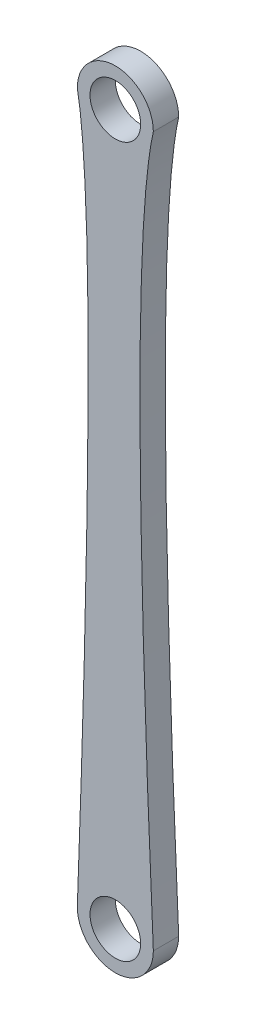
SolidWorks part; units mm, degrees
ref_plane "Front Plane" through (0, 0, 0) normal (0, 0, 1) x (1, 0, 0)
ref_plane "Top Plane" through (0, 0, 0) normal (0, 1, 0) x (1, 0, 0)
ref_plane "Right Plane" through (0, 0, 0) normal (1, 0, 0) x (0, 0, -1)
sketch "Sketch1" plane through (0, 0, 0) normal (0, 0, 1) x (1, 0, 0)
  line L0 (0, 204.7322) -> (0, -75.2678) construction
  circle A0 centre (0, -75.2678) radius 10
  circle A1 centre (0, 204.7322) radius 10
  arc A2 (-15, -75.2678) -> (15, -75.2678) centre (0, -75.2678) ccw
  arc A3 (15, 204.7322) -> (-15, 204.7322) centre (0, 204.7322) ccw
  spline S0 degree 2 poles (-15, 204.7322) (-6.4227, 158.4812) (-15, -75.2678) knots 0 0 0 1 1 1
  spline S1 degree 2 poles (15, 204.7322) (4.4238, 157.932) (15, -75.2678) knots 0 0 0 1 1 1
extrude "Boss-Extrude1" add sketch "Sketch1" along normal blind 10
ref_axis "Axis1" through (0, -75.2678, 10) along (0, 0, -1)
ref_axis "Axis2" through (0, 204.7322, 10) along (0, 0, -1)
